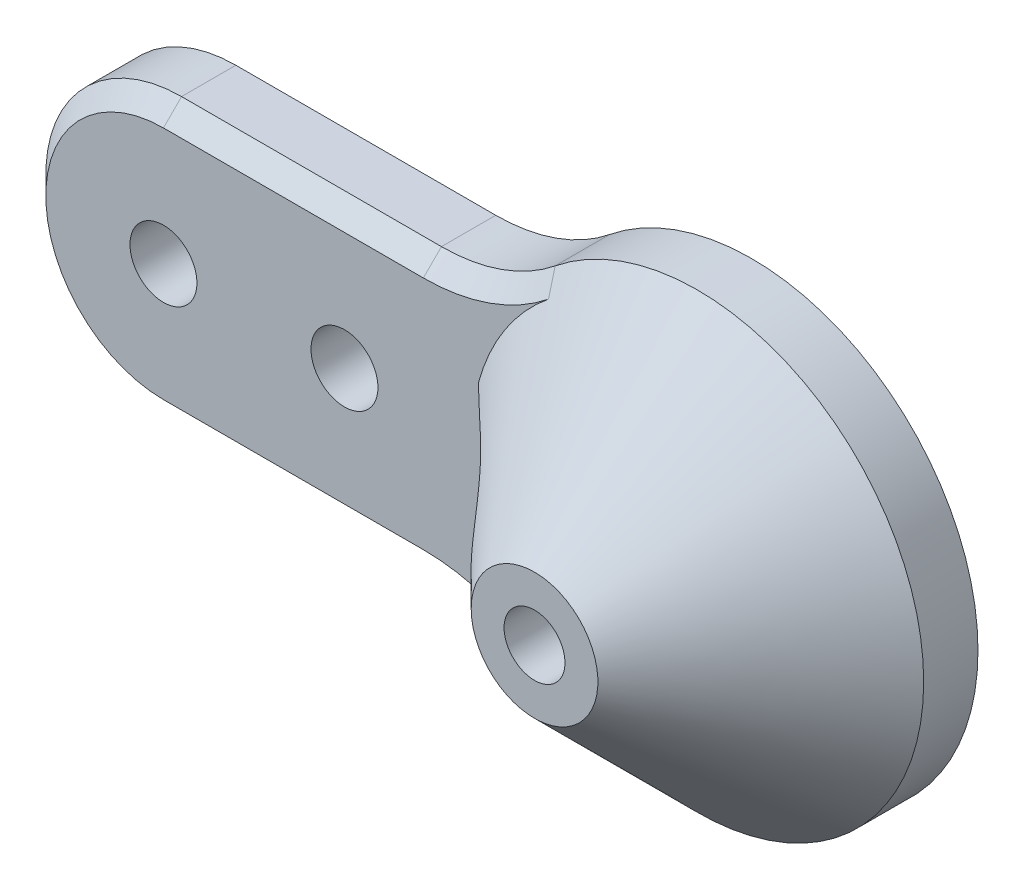
SolidWorks part; units mm, degrees
ref_plane "Front Plane" through (0, 0, 0) normal (0, 0, 1) x (1, 0, 0)
ref_plane "Top Plane" through (0, 0, 0) normal (0, 1, 0) x (1, 0, 0)
ref_plane "Right Plane" through (0, 0, 0) normal (1, 0, 0) x (0, 0, -1)
sketch "Sketch1" plane through (0, 0, 0) normal (0, 0, 1) x (1, 0, 0)
  line L3 (123.9, 7.5) -> (138.2579, 7.5)
  line L4 (123.9, -7.5) -> (138.2579, -7.5)
  arc A0 (144.5433, -9.7222) -> (144.5433, 9.7222) centre (152.4, 0) ccw
  arc A1 (138.2579, -7.5) -> (144.5433, -9.7222) centre (138.2579, -17.5) cw
  arc A3 (123.9, 7.5) -> (123.9, -7.5) centre (123.9, 0) ccw
  circle A4 centre (160.9, 0) radius 1.85
  circle A5 centre (160.9, 0) radius 1.85
  circle A6 centre (152.4, 0) radius 5
  circle A7 centre (152.4, 0) radius 5
  circle A8 centre (143.9, 0) radius 1.85
  circle A9 centre (143.9, 0) radius 1.85
  circle A10 centre (133.9, 0) radius 1.85
  circle A11 centre (133.9, 0) radius 1.85
  circle A12 centre (123.9, 0) radius 1.85
  circle A13 centre (123.9, 0) radius 1.85
  arc A14 (138.2579, 7.5) -> (144.5433, 9.7222) centre (138.2579, 17.5) ccw
  dimension "D1" = 10
  dimension "D7" = 15
  dimension "D8" = 25
  dimension "D2" = 0
  dimension "D3" = 0
  dimension "D4" = 0
  dimension "D5" = 0
  dimension "D6" = 0
extrude "Boss-Extrude1" add sketch "Sketch1" along normal blind 4
chamfer "Chamfer1" distance 1 angle 45 6 edges at (116.4, 0, 4) (131.0789, -7.5, 4) (131.0789, 7.5, 4) (141.5912, -8.0719, 4) (141.5912, 8.0719, 4) (164.9, 0, 4)
ref_axis "Axis1" through (152.4, 0, 4) along (0, 0, -1)
ref_plane "Plane1" through (152.4, 0, 0) normal (1, 0, 0) x (0, 0, -1)
sketch "Sketch3" plane through (152.4, 0, 0) normal (1, 0, 0) x (0, 0, -1)
  line L0 (-4, -6.5) -> (-4, -8.9444) construction
  line L1 (-4, -11.5) -> (-4, -5)
  line L3 (-4, -6.5) -> (-4, -8.9444) construction
  line L4 (-4, -11.5) -> (-12, -3.5)
  line L5 (-12, -3.5) -> (-12, -1.6833)
  line L6 (-12, -1.6833) -> (-9, -1.6833)
  line L7 (-9, -1.6833) -> (-9, -3.6716)
  line L8 (-9, -3.6716) -> (-7.6716, -5)
  line L9 (-7.6716, -5) -> (-4, -5)
  line L10 (0, 0) -> (-50000, 0) construction
  line L12 (-4, -11.5) -> (-3, -12.5) construction
  point P2 (-4, -5)
  dimension "D1" = 3.3667
  dimension "D2" = 7
  dimension "D3" = 3
  dimension "D4" = 2
  dimension "D5" = 10
revolve "Revolve2" add sketch "Sketch3" angle 360 about L10
sketch "Sketch4" plane through (0, 0, 4) normal (0, 0, -1) x (-1, 0, 0)
  line L0 (-143.9, -3) -> (-141.2982, -3)
  line L1 (-143.9, 3) -> (-141.2982, 3)
  arc A0 (-145.1718, -8.9444) -> (-145.1718, 8.9444) centre (-152.4, 0) ccw construction
  arc A2 (-143.9, 3) -> (-143.9, -3) centre (-143.9, 0) ccw
  arc A3 (-141.2982, -3) -> (-141.2982, 3) centre (-152.4, 0) ccw
  circle A4 centre (-143.9, 0) radius 1.85 construction
  dimension "D1" = 6
extrude "Cut-Extrude1" cut sketch "Sketch4" against normal through all contours A2 L0 A3 L1
sketch "Sketch5" plane through (0, 0, 0) normal (0, 0, -1) x (-1, 0, 0)
  circle A0 centre (-152.4, 0) radius 8.5 construction
  circle A2 centre (-152.4, -8.5) radius 1.85
  circle A3 centre (-152.4, 8.5) radius 1.85
  arc A4 (-144.5433, 9.7222) -> (-144.5433, -9.7222) centre (-152.4, 0) ccw construction
  point P11 (-152.4, 0)
  dimension "D1" = 17
  dimension "D2" = 3.7
  dimension "D3" = 2
extrude "Boss-Extrude2" [suppressed] add sketch "Sketch5" along normal blind 4
chamfer "Chamfer2" [suppressed] distance 1.7 angle 45
extrude "Cut-Extrude2" cut sketch "Sketch5<2>" against normal up to surface (4 mm away) up to face at (162.75, 0, 4)
sketch "Sketch5<2>" plane through (0, 0, 0) normal (0, 0, -1) x (-1, 0, 0) same geometry as "Sketch5"
